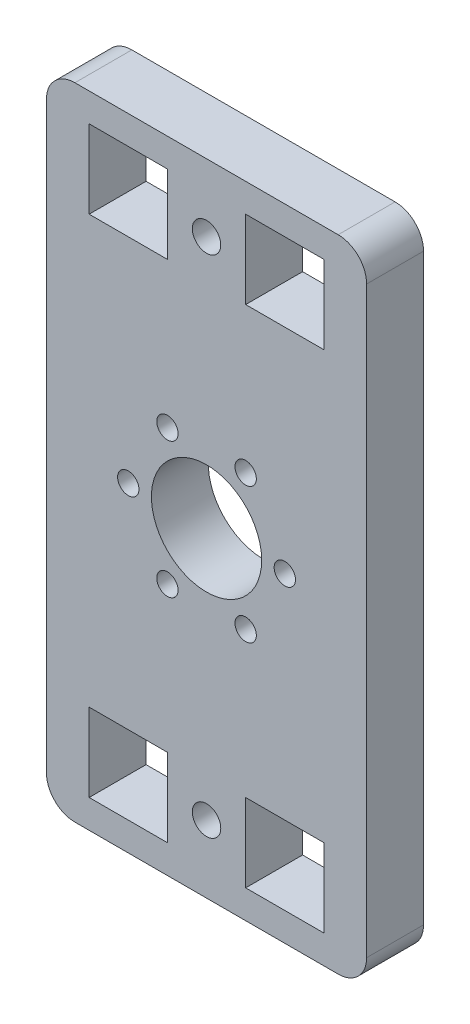
SolidWorks part; units mm, degrees
ref_plane "Front Plane" through (0, 0, 0) normal (0, 0, 1) x (1, 0, 0)
ref_plane "Top Plane" through (0, 0, 0) normal (0, 1, 0) x (1, 0, 0)
ref_plane "Right Plane" through (0, 0, 0) normal (1, 0, 0) x (0, 0, -1)
sketch "Sketch1" plane through (0, 0, 0) normal (0, 0, 1) x (1, 0, 0)
  line L0 (0, 0) -> (-11, 0) construction
  line L1 (18.5, -45) -> (-18.5, -45)
  line L2 (22.5, -41) -> (22.5, 41)
  line L3 (18.5, 45) -> (-18.5, 45)
  line L4 (-22.5, -41) -> (-22.5, 41)
  line L5 (22.5, -45) -> (-22.5, 45) construction
  line L6 (22.5, 45) -> (-22.5, -45) construction
  line L15 (0, 0) -> (0, -8.1671) construction
  line L16 (-16.5, -30) -> (-5.5, -30)
  line L17 (-16.5, -30) -> (-16.5, -41)
  line L18 (-16.5, -41) -> (-5.5, -41)
  line L19 (-5.5, -30) -> (-5.5, -41)
  line L20 (16.5, -41) -> (5.5, -41)
  line L21 (5.5, -30) -> (5.5, -41)
  line L22 (16.5, -30) -> (5.5, -30)
  line L23 (16.5, -30) -> (16.5, -41)
  line L24 (16.5, 30) -> (16.5, 41)
  line L25 (16.5, 30) -> (5.5, 30)
  line L26 (5.5, 30) -> (5.5, 41)
  line L27 (16.5, 41) -> (5.5, 41)
  line L28 (-16.5, 41) -> (-5.5, 41)
  line L29 (-5.5, 30) -> (-5.5, 41)
  line L30 (-16.5, 30) -> (-5.5, 30)
  line L31 (-16.5, 30) -> (-16.5, 41)
  circle A9 centre (0, 0) radius 7.75
  circle A10 centre (-11, 0) radius 1.5
  circle A11 centre (-5.5, 9.5263) radius 1.5
  circle A12 centre (5.5, 9.5263) radius 1.5
  circle A13 centre (11, 0) radius 1.5
  circle A14 centre (5.5, -9.5263) radius 1.5
  circle A15 centre (-5.5, -9.5263) radius 1.5
  circle A16 centre (0, -35.5) radius 2
  circle A17 centre (0, 35.5) radius 2
  arc A18 (18.5, -45) -> (22.5, -41) centre (18.5, -41) ccw
  arc A19 (-22.5, -41) -> (-18.5, -45) centre (-18.5, -41) ccw
  arc A20 (-22.5, 41) -> (-18.5, 45) centre (-18.5, 41) cw
  arc A21 (22.5, 41) -> (18.5, 45) centre (18.5, 41) ccw
  point P0 (0, 0)
  dimension "D5" = 5.5
  dimension "D8" = 4
  dimension "D9" = 0
  dimension "D11" = 35.5
  dimension "D16" = 15.5
  dimension "D19" = 3
  dimension "D10" = 4
  dimension "D2" = 45
  dimension "D3" = 11
  dimension "D4" = 45
  dimension "D6" = 11
  dimension "D7" = 30
  dimension "D17" = 11
  dimension "D18" = 0
  dimension "D21" = 11
  dimension "D22" = 11
  dimension "D20" = 6
extrude "Boss-Extrude2" add sketch "Sketch1" along normal blind 8
